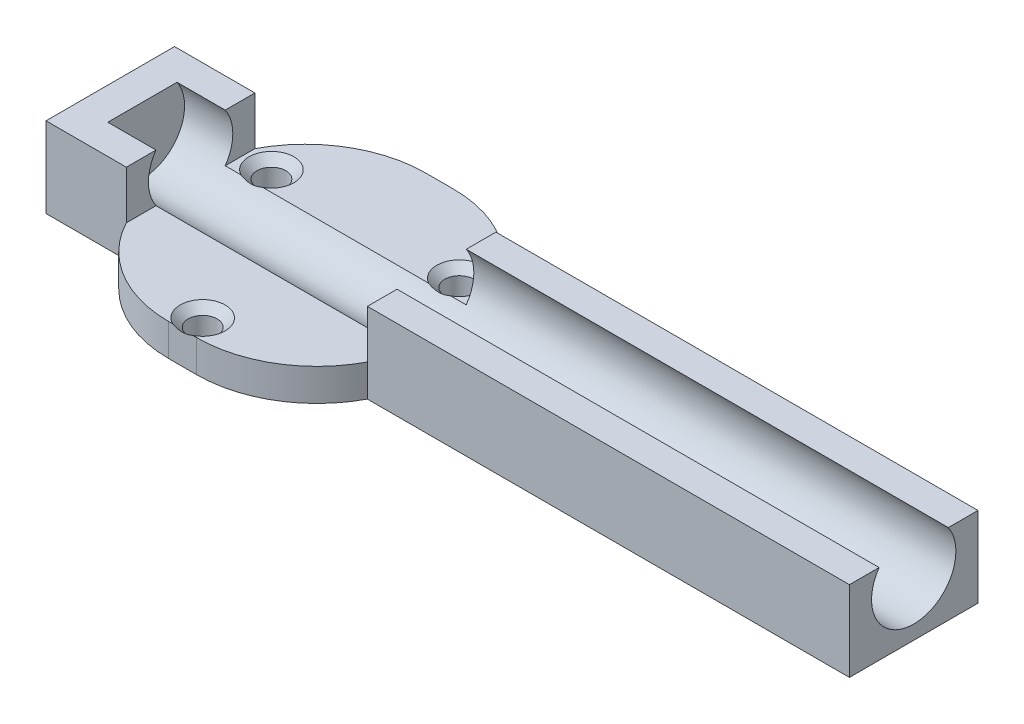
SolidWorks part; units mm, degrees
ref_plane "Спереди" through (0, 0, 0) normal (0, 0, 1) x (1, 0, 0)
ref_plane "Сверху" through (0, 0, 0) normal (0, 1, 0) x (1, 0, 0)
ref_plane "Справа" through (0, 0, 0) normal (1, 0, 0) x (0, 0, -1)
sketch "Эскиз6" plane through (0, 0, 0) normal (0, 1, 0) x (1, 0, 0)
  line L0 (0, 16) -> (0, 8)
  line L1 (0, 16) -> (30, 16)
  line L2 (30, 16) -> (30, 8)
  line L3 (30, 8) -> (90, 8)
  line L4 (90, 8) -> (90, -8)
  line L5 (0, 56.0118) -> (0, 0) construction
  line L6 (0, 0) -> (129.6915, 0) construction
  line L7 (0, 8) -> (-10, 8)
  line L8 (-10, 8) -> (-10, -8)
  line L9 (0, -16) -> (0, -8)
  line L10 (0, -8) -> (-10, -8)
  line L11 (30, -8) -> (90, -8)
  line L12 (30, -16) -> (30, -8)
  line L13 (0, -16) -> (30, -16)
  point P15 (-10, 0)
  point P16 (90, 0)
  dimension "D1" = 16
  dimension "D2" = 30
  dimension "D3" = 8
  dimension "D4" = 10
  dimension "D5" = 60
extrude "Бобышка-Вытянуть2" add sketch "Эскиз6" along normal blind 4
sketch "Эскиз7" plane through (0, 4, 0) normal (0, 1, 0) x (1, 0, 0)
  line L1 (-10, 8) -> (90, 8)
  line L2 (-10, 8) -> (-10, -8)
  line L3 (-10, -8) -> (90, -8)
  line L4 (90, 8) -> (90, -8)
extrude "Бобышка-Вытянуть3" add sketch "Эскиз7" along normal blind 6
sketch "Эскиз8" plane through (90, 0, 0) normal (1, 0, 0) x (0, 0, -1)
  line L0 (-8, 10) -> (8, 10) construction
  circle A0 centre (0, 7) radius 5.25
  dimension "D1" = 10.5
  dimension "D2" = 3
extrude "Вырез-Вытянуть3" cut sketch "Эскиз8" against normal offset from surface (96 mm away) 4 up to face at (-10, 5, 0)
sketch "Эскиз9" plane through (0, 0, 8) normal (0, 0, 1) x (1, 0, 0)
  line L0 (-10, 10) -> (90, 10) construction
  line L1 (0, 10) -> (30, 10)
  line L2 (0, 10) -> (0, 4)
  line L3 (0, 4) -> (30, 4)
  line L4 (30, 10) -> (30, 4)
  line L5 (-10, 10) -> (-10, 0) construction
  dimension "D1" = 10
extrude "Вырез-Вытянуть4" cut sketch "Эскиз9" against normal through all
sketch "Эскиз10" plane through (0, 4, 0) normal (0, 1, 0) x (1, 0, 0)
  line L0 (0, 0) -> (111.8319, 0) construction
  circle A0 centre (15, 0) radius 13.5 construction
  circle A1 centre (15, -13.5) radius 1.8
  circle A2 centre (3.3087, 6.75) radius 1.8
  circle A3 centre (26.6913, 6.75) radius 1.8
  point P7 (15, 0)
  point P14 (15, 0)
  dimension "D1" = 27
  dimension "D2" = 3.6
  dimension "D4" = 15
  dimension "D3" = 3
extrude "Вырез-Вытянуть5" cut sketch "Эскиз10" against normal through all
fillet "Скругление3" radius 15 4 edges at (30, 2, -16) (0, 2, -16) (30, 2, 16) (0, 2, 16)
chamfer "Фаска1" distance 1 angle 45 3 edges at (15, 4, 15.3) (3.3087, 4, -4.95) (26.6913, 4, -4.95)
